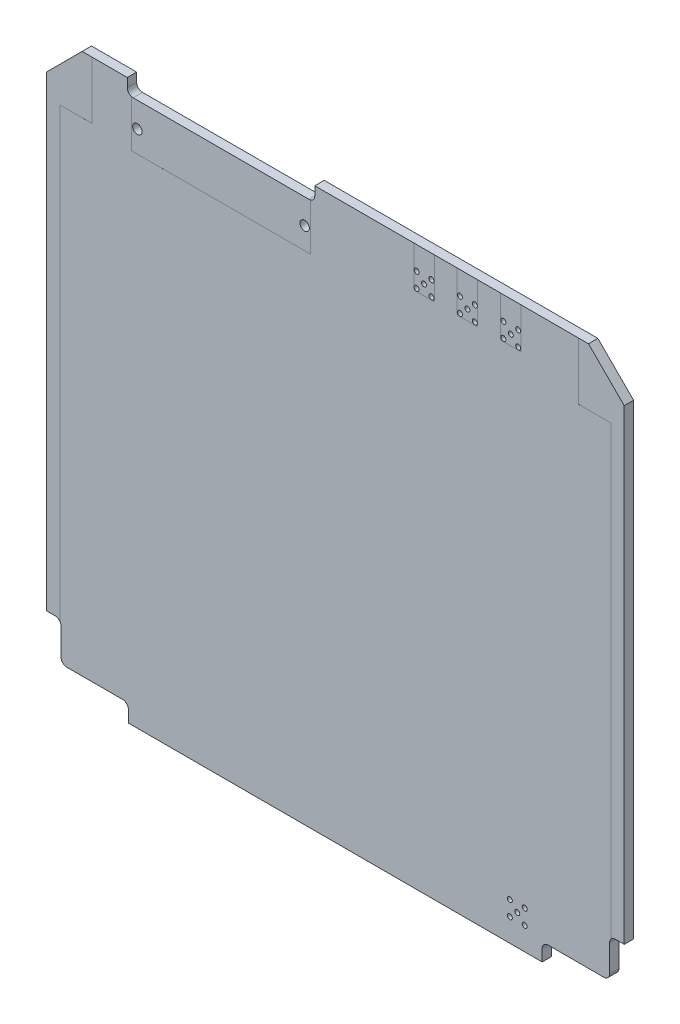
SolidWorks part; units mm, degrees
ref_plane "Front Plane" through (0, 0, 0) normal (0, 0, 1) x (1, 0, 0)
ref_plane "Top Plane" through (0, 0, 0) normal (0, 1, 0) x (1, 0, 0)
ref_plane "Right Plane" through (0, 0, 0) normal (1, 0, 0) x (0, 0, -1)
ref_plane "Plane4" through (0, 0, -0.0125) normal (0, 0, -1) x (-1, 0, 0)
sketch "Sketch1" plane through (0, 0, -0.0125) normal (0, 0, -1) x (-1, 0, 0)
  line L0 (35.3, -50) -> (35.3, -48)
  line L1 (36.3, -47) -> (45.8, -47)
  line L2 (46.8, -46) -> (46.8, -41.4)
  line L3 (47.8, -40.4) -> (49.3, -40.4)
  line L4 (49.3, -40.4) -> (49.3, 39.2)
  line L5 (49.3, 39.2) -> (43.2, 45.3)
  line L6 (43.2, 45.3) -> (35.5, 45.3)
  line L7 (35.5, 45.3) -> (35.5, 43.8)
  line L8 (34.5, 42.8) -> (4.5, 42.8)
  line L9 (3.5, 43.8) -> (3.5, 45.3)
  line L10 (3.5, 45.3) -> (-43.2, 45.3)
  line L11 (-43.2, 45.3) -> (-49.3, 39.2)
  line L12 (-49.3, 39.2) -> (-49.3, -40.4)
  line L13 (-49.3, -40.4) -> (-47.8, -40.4)
  line L14 (-46.8, -41.4) -> (-46.8, -46)
  line L15 (-45.8, -47) -> (-36.3, -47)
  line L16 (-35.3, -48) -> (-35.3, -50)
  line L17 (-35.3, -50) -> (35.3, -50)
  line L18 (0, -50) -> (0, 45.3) construction
  line L19 (19.5, 42.8) -> (19.5, 25.5258) construction
  line L20 (-13.87, 41.37) -> (-16.41, 38.83) construction
  line L21 (-21.27, 41.37) -> (-23.81, 38.83) construction
  line L22 (-28.67, 41.37) -> (-31.21, 38.83) construction
  arc A0 (35.3, -48) -> (36.3, -47) centre (36.3, -48) cw
  arc A1 (45.8, -47) -> (46.8, -46) centre (45.8, -46) ccw
  arc A2 (46.8, -41.4) -> (47.8, -40.4) centre (47.8, -41.4) cw
  arc A3 (35.5, 43.8) -> (34.5, 42.8) centre (34.5, 43.8) cw
  arc A4 (4.5, 42.8) -> (3.5, 43.8) centre (4.5, 43.8) cw
  arc A5 (-47.8, -40.4) -> (-46.8, -41.4) centre (-47.8, -41.4) cw
  arc A6 (-46.8, -46) -> (-45.8, -47) centre (-45.8, -46) ccw
  arc A7 (-36.3, -47) -> (-35.3, -48) centre (-36.3, -48) cw
  circle A8 centre (-21.27, 41.37) radius 0.425
  circle A9 centre (-23.81, 41.37) radius 0.425
  circle A10 centre (-22.54, 40.1) radius 0.425
  circle A11 centre (-13.87, 41.37) radius 0.425
  circle A12 centre (-23.81, 38.83) radius 0.425
  circle A13 centre (-16.41, 41.37) radius 0.425
  circle A14 centre (-15.14, 40.1) radius 0.425
  circle A15 centre (-21.27, 38.83) radius 0.425
  circle A16 centre (-28.67, 41.37) radius 0.425
  circle A17 centre (-31.21, 41.37) radius 0.425
  circle A18 centre (-16.41, 38.83) radius 0.425
  circle A19 centre (-29.94, 40.1) radius 0.425
  circle A20 centre (-31.21, 38.83) radius 0.425
  circle A21 centre (-28.67, 38.83) radius 0.425
  circle A22 centre (33.775, 38.54) radius 0.8
  circle A23 centre (5.225, 38.54) radius 0.8
  circle A24 centre (-13.87, 38.83) radius 0.425
  point P35 (-15.14, 40.1)
  dimension "D7" = 2.5
  dimension "D8" = 1.6
  dimension "D9" = 14.275
  dimension "D10" = 4.26
  dimension "D11" = 1
  dimension "D12" = 1
  dimension "D13" = 1
  dimension "D14" = 1
  dimension "D15" = 1
  dimension "D16" = 1
  dimension "D17" = 1
  dimension "D18" = 1
  dimension "D26" = 0.85
  dimension "D1" = 98.6
  dimension "D2" = 95.3
  dimension "D3" = 14
  dimension "D4" = 9.6
  dimension "D5" = 2.5
  dimension "D6" = 3
  dimension "D19" = 14
  dimension "D20" = 2.5
  dimension "D21" = 6.1
  dimension "D22" = 6.1
  dimension "D23" = 32
  dimension "D24" = 2.54
  dimension "D25" = 2.54
  dimension "D28" = 7.4
  dimension "D29" = 3.93
  dimension "D30" = 35.43
  dimension "D31" = 45
  dimension "D32" = 45
  dimension "D33" = 29.8
  dimension "D34" = 50
  dimension "D27" = 3
extrude "Boss-Extrude1" add sketch "Sketch1" against normal blind 1.6
sketch "thermalContacts_lower" plane through (0, 0, -0.0125) normal (0, 0, -1) x (-1, 0, 0)
  line L0 (47, 35.5) -> (47, -41.5) construction
  line L1 (41.5, 35.5) -> (41.5, 41.5) construction
  line L2 (41.5, 35.5) -> (47, 35.5) construction
  line L3 (47, 35.5) -> (47, -41.5)
  line L4 (41.5, 35.5) -> (41.5, 41.5)
  line L5 (41.5, 35.5) -> (47, 35.5)
  line L6 (-47, 35.5) -> (-47, -41.5) construction
  line L7 (-41.5, 35.5) -> (-47, 35.5) construction
  line L8 (-41.5, 35.5) -> (-41.5, 41.5) construction
  line L9 (-47, 35.5) -> (-47, -41.5)
  line L10 (-41.5, 35.5) -> (-47, 35.5)
  line L11 (-41.5, 35.5) -> (-41.5, 41.5)
  line L12 (-41.5, 41.5) -> (-41.5, 47) construction
  line L13 (-41.5, 41.5) -> (-49.5, 41.5) construction
  line L14 (-41.5, 41.5) -> (-41.5, 47)
  line L15 (-41.5, 41.5) -> (-49.5, 41.5) construction
  line L16 (41.5, 41.5) -> (41.5, 47) construction
  line L17 (41.5, 41.5) -> (49.5, 41.5) construction
  line L18 (41.5, 41.5) -> (41.5, 47)
  line L19 (41.5, 41.5) -> (49.5, 41.5) construction
  line L20 (47, -41.5) -> (59.8273, -41.5)
  line L21 (59.8273, -41.5) -> (59.8273, 47)
  line L22 (-56.1922, 47) -> (-41.5, 47)
  line L23 (41.5, 47) -> (59.8273, 47)
  line L24 (-56.1922, 47) -> (-56.1922, -41.5)
  line L25 (-47, -41.5) -> (-56.1922, -41.5)
sketch "thermalContacts_upper" plane through (0, 0, 1.5875) normal (0, 0, 1) x (1, 0, 0)
  line L3 (-47, 35.5) -> (-47, -41.5)
  line L4 (-41.5, 35.5) -> (-41.5, 41.5)
  line L5 (-41.5, 35.5) -> (-47, 35.5)
  line L9 (47, 35.5) -> (47, -41.5)
  line L10 (41.5, 35.5) -> (47, 35.5)
  line L11 (41.5, 35.5) -> (41.5, 41.5)
  line L14 (41.5, 41.5) -> (41.5, 47)
  line L15 (41.5, 41.5) -> (49.5, 41.5) construction
  line L18 (-41.5, 41.5) -> (-41.5, 47)
  line L19 (-41.5, 41.5) -> (-49.5, 41.5) construction
  line L20 (47, -41.5) -> (59.8273, -41.5)
  line L21 (59.8273, -41.5) -> (59.8273, 47)
  line L22 (59.8273, 47) -> (41.5, 47)
  line L23 (-41.5, 47) -> (-56.1922, 47)
  line L24 (-56.1922, 47) -> (-56.1922, -41.5)
  line L25 (-56.1922, -41.5) -> (-47, -41.5)
extrude "Cut-Extrude1" cut sketch "thermalContacts_lower" against normal blind 0.0001
extrude "Cut-Extrude2" cut sketch "thermalContacts_upper" against normal blind 0.0001
sketch "partFootprints" plane through (0, 0, 1.5875) normal (0, 0, 1) x (1, 0, 0)
  line L0 (-34.74, 34.84) -> (-34.74, 42.8292)
  line L1 (-4.26, 34.84) -> (-34.74, 34.84)
  line L2 (-41.5, 45.3) -> (-35.5, 45.3) construction
  line L3 (-36.1132, 45.3) -> (-39.5054, 45.3) construction
  line L4 (-4.26, 34.84) -> (-4.26, 42.8292)
  line L5 (-49.3, -40.4) -> (-49.3, 39.2) construction
  line L6 (13.39, 45.3) -> (13.39, 38.35)
  line L7 (13.39, 38.35) -> (16.89, 38.35)
  line L8 (16.89, 38.35) -> (16.89, 45.3)
  line L9 (16.89, 45.3) -> (13.39, 45.3)
  line L10 (20.79, 45.3) -> (20.79, 38.35)
  line L11 (20.79, 38.35) -> (24.29, 38.35)
  line L12 (24.29, 38.35) -> (24.29, 45.3)
  line L13 (24.29, 45.3) -> (20.79, 45.3)
  line L14 (28.19, 45.3) -> (28.19, 38.35)
  line L15 (28.19, 38.35) -> (31.69, 38.35)
  line L16 (31.69, 38.35) -> (31.69, 45.3)
  line L17 (31.69, 45.3) -> (28.19, 45.3)
  line L19 (14.12, 38.35) -> (16.16, 38.35) construction
  line L20 (-34.74, 42.8292) -> (-4.26, 42.8292)
  line L21 (-3.5, 45.3) -> (41.5, 45.3) construction
  line L22 (14.12, 38.35) -> (16.16, 38.35) construction
  line L23 (13.39, 41.85) -> (13.39, 38.35) construction
  line L24 (16.89, 41.85) -> (16.89, 38.35) construction
  line L25 (13.39, 41.85) -> (13.39, 38.35) construction
  line L26 (16.89, 41.85) -> (16.89, 38.35) construction
  arc A0 (-35.5, 43.8) -> (-34.5, 42.8) centre (-34.5, 43.8) ccw construction
  arc A1 (-4.5, 42.8) -> (-3.5, 43.8) centre (-4.5, 43.8) ccw construction
  dimension "D1" = 10.46
  dimension "D2" = 14.56
  dimension "D3" = 30.48
  dimension "D7" = 7.4
  dimension "D6" = 3
extrude "Cut-Extrude3" cut sketch "partFootprints" against normal blind 0.0001
sketch "Sketch2" plane through (0, 0, 1.5875) normal (0, 0, 1) x (1, 0, 0)
  line L0 (35.1, -50) -> (35.1, -24.8165) construction
  line L1 (35.3, -50) -> (-35.3, -50) construction
  line L2 (27, -50) -> (27, -24.8165) construction
  line L3 (35.3, -48) -> (35.3, -50) construction
  line L4 (32.32, -43.53) -> (29.78, -46.07) construction
  line L5 (27, -44.8) -> (35.1, -44.8) construction
  circle A0 centre (32.32, -43.53) radius 0.425
  circle A1 centre (29.78, -43.53) radius 0.425
  circle A2 centre (31.05, -44.8) radius 0.425
  circle A3 centre (29.78, -46.07) radius 0.425
  circle A4 centre (32.32, -46.07) radius 0.425
  point P8 (35.3, -49)
  point P9 (31.05, -44.8)
  point P20 (31.05, -44.8)
  dimension "D5" = 0.85
  dimension "D1" = 0.2
  dimension "D2" = 8.3
  dimension "D3" = 2.54
  dimension "D4" = 2.54
  dimension "D6" = 3.93
extrude "Cut-Extrude4" cut sketch "Sketch2" against normal through all
